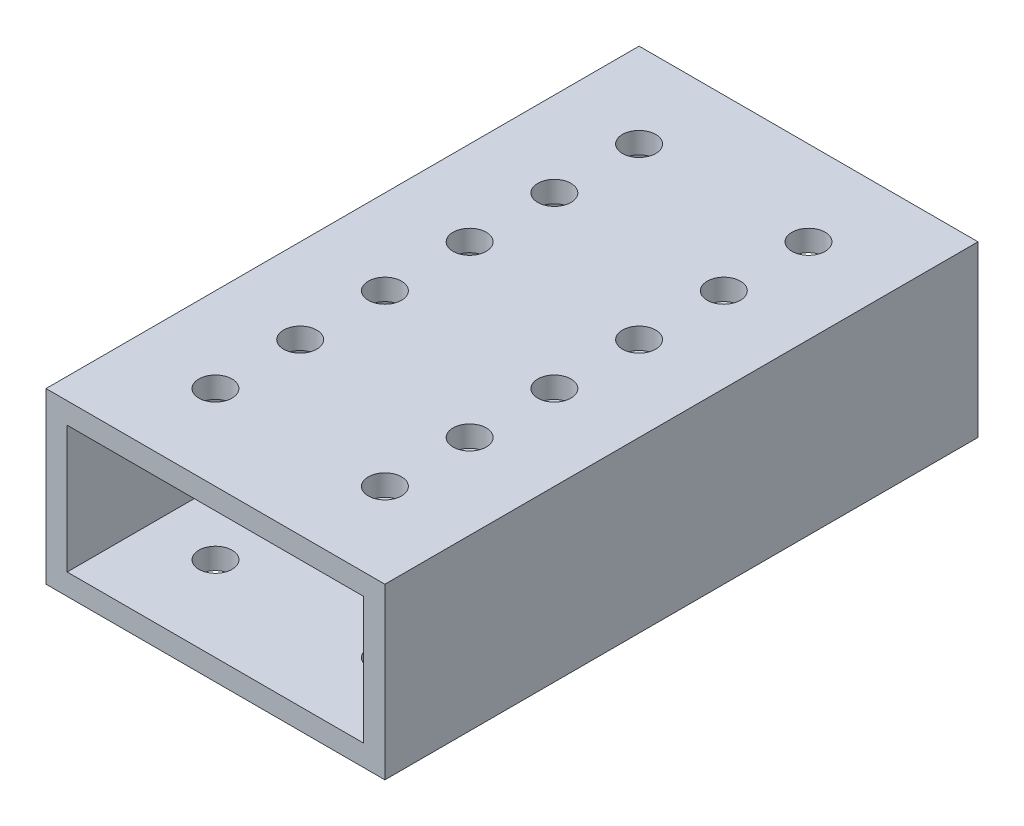
SolidWorks part; units mm, degrees
ref_plane "Front Plane" through (0, 0, 0) normal (0, 0, 1) x (1, 0, 0)
ref_plane "Top Plane" through (0, 0, 0) normal (0, 1, 0) x (1, 0, 0)
ref_plane "Right Plane" through (0, 0, 0) normal (1, 0, 0) x (0, 0, -1)
sketch "Sketch1" plane through (0, 0, 0) normal (0, 0, 1) x (1, 0, 0)
  line L1 (-25.4, -12.7) -> (25.4, -12.7)
  line L2 (-25.4, -12.7) -> (-25.4, 12.7)
  line L3 (-25.4, 12.7) -> (25.4, 12.7)
  line L4 (25.4, -12.7) -> (25.4, 12.7)
  line L5 (-25.4, -12.7) -> (25.4, 12.7) construction
  line L6 (-25.4, 12.7) -> (25.4, -12.7) construction
  point P0 (0, 0)
  dimension "D1" = 50.8
  dimension "D2" = 25.4
extrude "Boss-Extrude1" add sketch "Sketch1" along normal mid plane 88.9
shell "Shell1" thickness 3.175 removed face at (0, 0, -44.45) removed face at (0, 0, 44.45)
sketch "Sketch2" plane through (0, 0, 0) normal (0, 1, 0) x (1, 0, 0)
  line L0 (25.4, 44.45) -> (-25.4, 44.45) construction
  line L1 (-25.4, -44.45) -> (-25.4, 44.45) construction
  circle A0 centre (-12.7, 31.75) radius 2.4892
  circle A1 centre (12.7, 31.75) radius 2.4892
  circle A2 centre (12.7, 19.05) radius 2.4892
  circle A3 centre (12.7, 6.35) radius 2.4892
  circle A4 centre (12.7, -6.35) radius 2.4892
  circle A5 centre (12.7, -19.05) radius 2.4892
  circle A6 centre (12.7, -31.75) radius 2.4892
  circle A7 centre (-12.7, 19.05) radius 2.4892
  circle A8 centre (-12.7, 6.35) radius 2.4892
  circle A9 centre (-12.7, -6.35) radius 2.4892
  circle A10 centre (-12.7, -19.05) radius 2.4892
  circle A11 centre (-12.7, -31.75) radius 2.4892
  dimension "D1" = 4.9784
  dimension "D7" = 12.7
  dimension "D2" = 12.7
  dimension "D3" = 12.7
  dimension "D6" = 25.4
  dimension "D4" = 2
  dimension "D5" = 6
extrude "Cut-Extrude1" cut sketch "Sketch2" against normal mid plane 127
